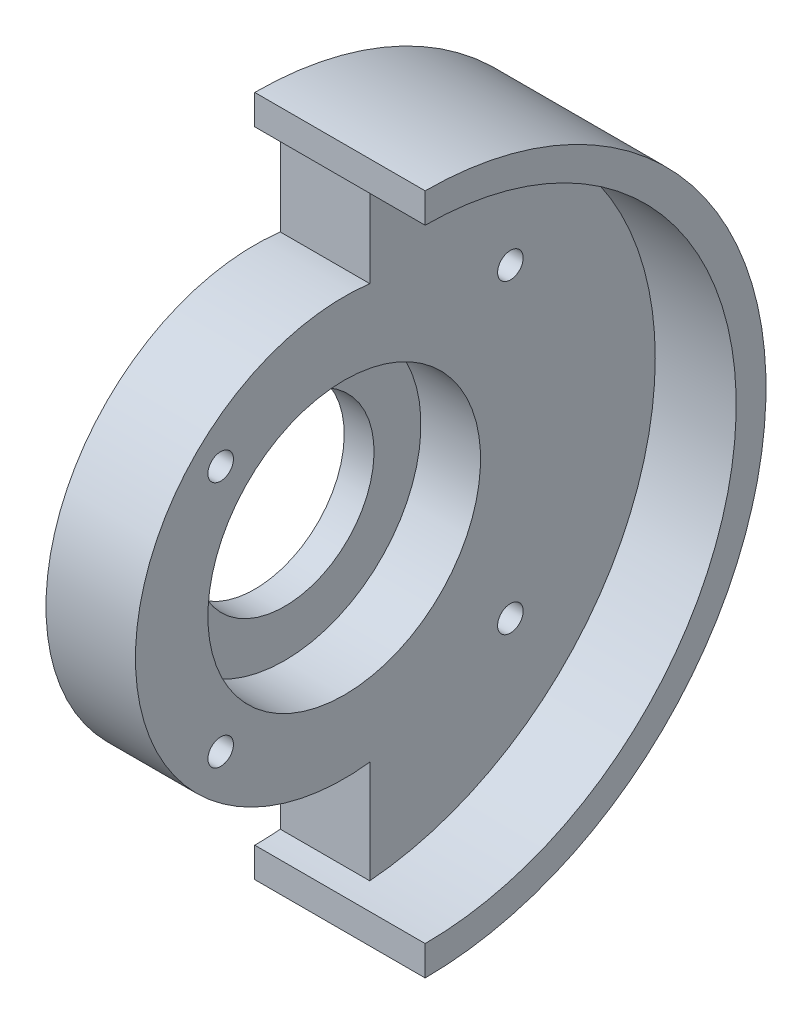
SolidWorks part; units mm, degrees
ref_plane "Front Plane" through (0, 0, 0) normal (0, 0, 1) x (1, 0, 0)
ref_plane "Top Plane" through (0, 0, 0) normal (0, 1, 0) x (1, 0, 0)
ref_plane "Right Plane" through (0, 0, 0) normal (1, 0, 0) x (0, 0, -1)
sketch "Sketch1" plane through (0, 0, 0) normal (0, 0, 1) x (1, 0, 0)
  line L0 (20, 40) -> (20, 36.5)
  line L1 (20, 36.5) -> (10.5, 36.5)
  line L2 (10.5, 36.5) -> (10.5, 16)
  line L3 (10.5, 16) -> (3.5, 16)
  line L4 (3.5, 16) -> (3.5, 10.5)
  line L5 (3.5, 10.5) -> (0, 10.5)
  line L6 (0, 10.5) -> (0, 40)
  line L7 (0, 40) -> (20, 40)
  line L8 (20, 0) -> (0, 0) construction
  dimension "D1" = 20
  dimension "D2" = 7
  dimension "D3" = 9.5
  dimension "D4" = 10.5
  dimension "D5" = 16
  dimension "D6" = 36.5
  dimension "D7" = 40
revolve "Revolve1" add sketch "Sketch1" angle 360 about L8
sketch "Sketch2" plane through (10.5, 0, 0) normal (1, 0, 0) x (0, 0, -1)
  line L0 (3, 24.3156) -> (3, 36.3765)
  line L1 (3, -24.3156) -> (3, -36.3765)
  line L2 (0, 40) -> (0, 36.5)
  line L3 (0, -36.5) -> (0, -40)
  arc A0 (3, 36.3765) -> (0, 36.5) centre (0, 0) ccw
  arc A1 (3, 24.3156) -> (3, -24.3156) centre (0, 0) ccw
  circle A2 centre (-14.4957, 14.4957) radius 1.5
  circle A3 centre (0, 0) radius 36.5 construction
  arc A4 (3, 24.3156) -> (3, -24.3156) centre (0, 0) ccw construction
  circle A5 centre (19.5, -17.9444) radius 1.5
  circle A6 centre (19.5, 17.9444) radius 1.5
  circle A7 centre (19.5, 17.9444) radius 1.5 construction
  circle A9 centre (19.5, -17.9444) radius 1.5 construction
  arc A10 (0, 40) -> (0, -40) centre (0, 0) ccw
  circle A11 centre (0, 0) radius 40 construction
  arc A12 (0, -36.5) -> (3, -36.3765) centre (0, 0) ccw
  circle A13 centre (-14.4957, 14.4957) radius 1.5 construction
  circle A14 centre (-14.4957, -14.4957) radius 1.5
  circle A15 centre (-14.4957, -14.4957) radius 1.5 construction
extrude "Cut-Extrude1" cut sketch "Sketch2" against normal through all both and the other way through all
sketch "Sketch3" plane through (0, 0, 0) normal (-1, 0, 0) x (0, 0, 1)
  circle A0 centre (-19.5, 17.9444) radius 2.75
  circle A1 centre (14.4957, 14.4957) radius 2.75
  circle A2 centre (-19.5, -17.9444) radius 2.75
  circle A3 centre (14.4957, -14.4957) radius 2.75
  dimension "D1" = 5.5
extrude "Cut-Extrude2" cut sketch "Sketch3" against normal blind 5
